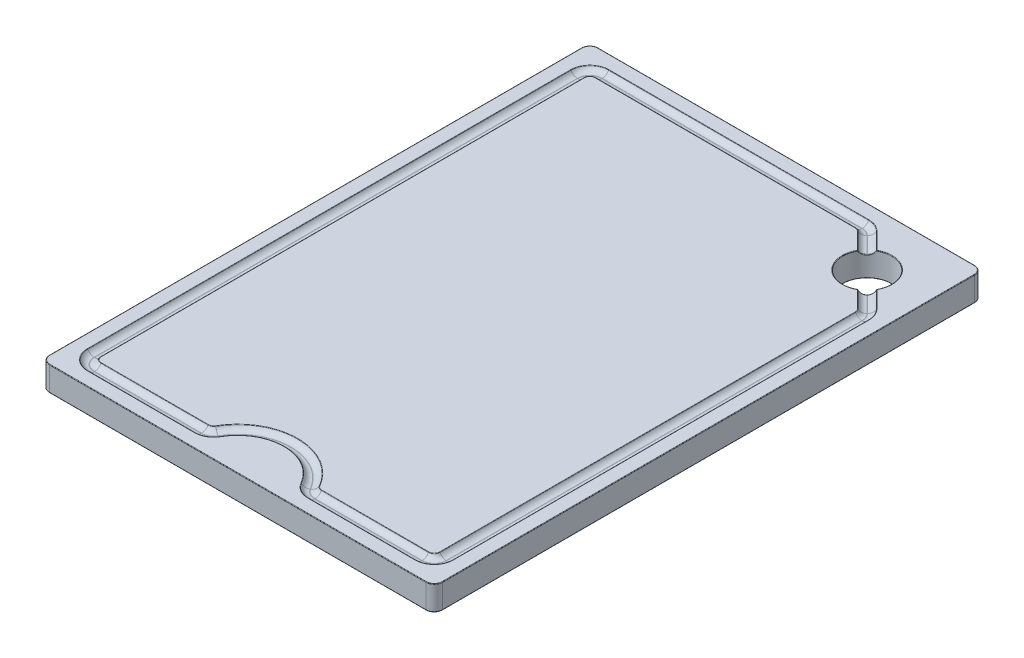
SolidWorks part; units mm, degrees
material "Oak"
ref_plane "Front Plane" through (0, 0, 0) normal (0, 0, 1) x (1, 0, 0)
ref_plane "Top Plane" through (0, 0, 0) normal (0, 1, 0) x (1, 0, 0)
ref_plane "Right Plane" through (0, 0, 0) normal (1, 0, 0) x (0, 0, -1)
sketch "KrausKorePlanSketch" plane through (0, 0, 0) normal (0, 1, 0) x (1, 0, 0)
  line L0 (419.1, 558.8) -> (419.1, 0) construction
  line L1 (0, 0) -> (838.2, 0)
  line L2 (0, 0) -> (0, 558.8)
  line L3 (0, 558.8) -> (838.2, 558.8)
  line L4 (838.2, 0) -> (838.2, 558.8)
  line L5 (0, 279.4) -> (838.2, 279.4) construction
  line L6 (25.4, 241.3) -> (812.8, 241.3) construction
  line L7 (25.4, 457.2) -> (812.8, 457.2)
  line L8 (25.4, 457.2) -> (25.4, 25.4)
  line L9 (25.4, 25.4) -> (812.8, 25.4)
  line L10 (812.8, 457.2) -> (812.8, 25.4)
  line L11 (419.1, 508) -> (749.3, 508) construction
  line L12 (749.3, 558.8) -> (749.3, 457.2) construction
  line L14 (812.8, 444.5) -> (25.4, 444.5)
  line L17 (812.8, 38.1) -> (25.4, 38.1)
  circle A0 centre (685.8, 317.5) radius 44.45
  circle A1 centre (419.1, 508) radius 17.4625
  circle A2 centre (749.3, 508) radius 17.4625
  point P13 (419.1, 457.2)
  dimension "D6" = 88.9
  dimension "D8" = 34.925
  dimension "D1" = 838.2
  dimension "D2" = 558.8
  dimension "D3" = 431.8
  dimension "D4" = 787.4
  dimension "D5" = 101.6
  dimension "D7" = 127
  dimension "D9" = 12.7
  dimension "D10" = 406.4
  dimension "D11" = 127
  dimension "D12" = 50.8
  dimension "D13" = 88.9
sketch "CuttingBoardSketch" plane through (0, 0, 0) normal (0, 1, 0) x (1, 0, 0)
  line L0 (25.4, 241.3) -> (812.8, 241.3) construction
  line L1 (28.575, 454.025) -> (333.375, 454.025)
  line L2 (28.575, 454.025) -> (28.575, 28.575)
  line L3 (28.575, 28.575) -> (333.375, 28.575)
  line L4 (333.375, 454.025) -> (333.375, 28.575)
  line L6 (25.4, 457.2) -> (25.4, 25.4) construction
  line L7 (317.5, 53.975) -> (317.5, 376.2609)
  line L8 (314.7102, 382.9961) -> (262.3461, 435.3602)
  line L9 (255.6109, 438.15) -> (53.975, 438.15)
  line L10 (44.45, 428.625) -> (44.45, 53.975)
  line L11 (53.975, 44.45) -> (136.9809, 44.45)
  line L12 (180.975, 69.85) -> (180.975, 28.575) construction
  line L13 (224.9691, 44.45) -> (307.975, 44.45)
  line L14 (255.6109, 443.3094) -> (53.975, 443.3094)
  line L15 (39.2906, 428.625) -> (39.2906, 53.975)
  line L16 (53.975, 39.2906) -> (136.9809, 39.2906)
  line L17 (224.9691, 39.2906) -> (307.975, 39.2906)
  line L18 (322.6594, 53.975) -> (322.6594, 376.2609)
  line L19 (318.3584, 386.6443) -> (265.9943, 439.0084)
  line L20 (255.6109, 432.9906) -> (53.975, 432.9906)
  line L21 (49.6094, 428.625) -> (49.6094, 53.975)
  line L22 (53.975, 49.6094) -> (136.9809, 49.6094)
  line L23 (224.9691, 49.6094) -> (307.975, 49.6094)
  line L24 (312.3406, 53.975) -> (312.3406, 376.2609)
  line L25 (311.062, 379.3478) -> (258.6978, 431.712)
  arc A0 (145.2298, 49.2125) -> (216.7202, 49.2125) centre (180.975, 28.575) cw
  circle A1 centre (288.5281, 409.1781) radius 19.05
  arc A2 (44.45, 53.975) -> (53.975, 44.45) centre (53.975, 53.975) ccw
  arc A3 (136.9809, 44.45) -> (145.2298, 49.2125) centre (136.9809, 53.975) ccw
  arc A4 (216.7202, 49.2125) -> (224.9691, 44.45) centre (224.9691, 53.975) ccw
  arc A5 (317.5, 53.975) -> (307.975, 44.45) centre (307.975, 53.975) cw
  arc A6 (317.5, 376.2609) -> (314.7102, 382.9961) centre (307.975, 376.2609) ccw
  arc A7 (255.6109, 438.15) -> (262.3461, 435.3602) centre (255.6109, 428.625) cw
  arc A8 (44.45, 428.625) -> (53.975, 438.15) centre (53.975, 428.625) cw
  arc A9 (39.2906, 428.625) -> (53.975, 443.3094) centre (53.975, 428.625) cw
  arc A10 (39.2906, 53.975) -> (53.975, 39.2906) centre (53.975, 53.975) ccw
  arc A11 (136.9809, 39.2906) -> (149.698, 46.6328) centre (136.9809, 53.975) ccw
  arc A12 (149.698, 46.6328) -> (212.252, 46.6328) centre (180.975, 28.575) cw
  arc A13 (212.252, 46.6328) -> (224.9691, 39.2906) centre (224.9691, 53.975) ccw
  arc A14 (322.6594, 53.975) -> (307.975, 39.2906) centre (307.975, 53.975) cw
  arc A15 (322.6594, 376.2609) -> (318.3584, 386.6443) centre (307.975, 376.2609) ccw
  arc A16 (255.6109, 443.3094) -> (265.9943, 439.0084) centre (255.6109, 428.625) cw
  arc A17 (49.6094, 428.625) -> (53.975, 432.9906) centre (53.975, 428.625) cw
  arc A18 (49.6094, 53.975) -> (53.975, 49.6094) centre (53.975, 53.975) ccw
  arc A19 (136.9809, 49.6094) -> (140.7617, 51.7922) centre (136.9809, 53.975) ccw
  arc A20 (140.7617, 51.7922) -> (221.1883, 51.7922) centre (180.975, 28.575) cw
  arc A21 (221.1883, 51.7922) -> (224.9691, 49.6094) centre (224.9691, 53.975) ccw
  arc A22 (312.3406, 53.975) -> (307.975, 49.6094) centre (307.975, 53.975) cw
  arc A23 (312.3406, 376.2609) -> (311.062, 379.3478) centre (307.975, 376.2609) ccw
  arc A24 (255.6109, 432.9906) -> (258.6978, 431.712) centre (255.6109, 428.625) cw
  point P4 (333.375, 241.3)
  point P22 (142.875, 44.45)
  point P27 (219.075, 44.45)
  point P36 (180.975, 69.85)
  dimension "D10" = 38.1
  dimension "D12" = 9.525
  dimension "D1" = 304.8
  dimension "D2" = 425.45
  dimension "D3" = 3.175
  dimension "D4" = 15.875
  dimension "D5" = 15.875
  dimension "D6" = 15.875
  dimension "D7" = 15.875
  dimension "D8" = 41.275
  dimension "D9" = 135
  dimension "D11" = 44.8469
  dimension "D13" = 5.1594
  dimension "D14" = 5.1594
extrude "BoardBoss-Extrude" add sketch "CuttingBoardSketch" against normal blind 15.875 and the other way blind 3.175 contours L4 L3 L2 L1
extrude "BoardDrainCut-Extrude" cut sketch "CuttingBoardSketch<3>" against normal blind 3.175 from offset 3.175 contours L20 A24 L25 A1 L8 A7 L9 A8 L10 A2 L11 A3 A0 A4 L13 A5 L7 A6 A23 L24 A22 L23 A21 A20 A19 L22 A18 L21 A17 | A0 L12 A12 A13 L17 A14 L18 A15 L19 A1 L8 A6 L7 A5 L13 A4 | L12 A0 A3 L11 A2 L10 A8 L9 A7 L8 A1 L19 A16 L14 A9 L15 A10 L16 A11 A12 | L25 A1 L8 | L8 A1 L19 region at (160.5678, 0, -63.9214) region at (184.8491, 0, -67.2703) region at (157.9419, 0, -68.4695) region at (290.3408, 0, -410.9908) region at (286.7155, 0, -407.3655)
sketch "CuttingBoardSketch<3>" plane through (0, 0, 0) normal (0, 1, 0) x (1, 0, 0) same geometry as "CuttingBoardSketch"
fillet "BoardDrainFillet" radius 5.5562 28 edges at (257.2815, 0, -432.6583) (154.7929, 0, -432.9906) (50.888, 0, -431.712) (49.6094, 0, -241.3) (50.888, 0, -50.888) (95.478, 0, -49.6094) (139.1637, 0, -50.1943) (180.975, 0, -75.0094) (222.7863, 0, -50.1943) (266.472, 0, -49.6094) (311.062, 0, -50.888) (312.3406, 0, -215.1179) (312.0083, 0, -377.9315) (284.8799, 0, -405.5299) (95.478, 0, -39.2906) (43.5916, 0, -43.5916) (39.2906, 0, -241.3) (43.5916, 0, -439.0084) (154.7929, 0, -443.3094) (261.2303, 0, -442.1916) (292.1764, 0, -412.8264) (321.5416, 0, -381.8803) (322.6594, 0, -215.1179) (318.3584, 0, -43.5916) (266.472, 0, -39.2906) (217.6269, 0, -41.258) (180.975, 0, -64.6906) (144.3231, 0, -41.258)
extrude "BoardHoleCut-Extrude" cut sketch "CuttingBoardSketch<4>" against normal through all and the other way through all contours A1
sketch "CuttingBoardSketch<4>" plane through (0, 0, 0) normal (0, 1, 0) x (1, 0, 0) same geometry as "CuttingBoardSketch"
fillet "BoardCornersFillet" radius 6.35 4 edges at (333.375, -6.35, -28.575) (28.575, -6.35, -28.575) (28.575, -6.35, -454.025) (333.375, -6.35, -454.025)
fillet "FinishingFillet" radius 0.3969 55 edges at (273.3779, 0.5486, -420.7269) (275.0577, 0, -422.6485) (277.7875, 1.1549, -424.9116) (303.6783, 0.5486, -397.6294) (301.9985, 0, -395.7077) (299.2688, 1.1549, -393.4447) (331.5151, -15.875, -452.1651) (180.975, -15.875, -454.025) (30.4349, -15.875, -452.1651) (28.575, -15.875, -241.3) (30.4349, -15.875, -30.4349) (180.975, -15.875, -28.575) (331.5151, -15.875, -30.4349) (333.375, -15.875, -241.3) (288.5281, -15.875, -390.1281) (312.0083, 3.175, -377.9315) (312.3406, 3.175, -215.1179) (311.062, 3.175, -50.888) (266.472, 3.175, -49.6094) (222.7863, 3.175, -50.1943) (180.975, 3.175, -75.0094) (139.1637, 3.175, -50.1943) (95.478, 3.175, -49.6094) (50.888, 3.175, -50.888) (49.6094, 3.175, -241.3) (50.888, 3.175, -431.712) (154.7929, 3.175, -432.9906) (257.2815, 3.175, -432.6583) (265.3054, 3.175, -425.1044) (275.0577, 3.175, -395.7077) (304.4544, 3.175, -385.9554) (30.4349, 3.175, -30.4349) (28.575, 3.175, -241.3) (30.4349, 3.175, -452.1651) (180.975, 3.175, -454.025) (331.5151, 3.175, -452.1651) (333.375, 3.175, -241.3) (331.5151, 3.175, -30.4349) (180.975, 3.175, -28.575) (261.2303, 3.175, -442.1916) (154.7929, 3.175, -443.3094) (43.5916, 3.175, -439.0084) (39.2906, 3.175, -241.3) (43.5916, 3.175, -43.5916) (95.478, 3.175, -39.2906) (144.3231, 3.175, -41.258) (180.975, 3.175, -64.6906) (217.6269, 3.175, -41.258) (266.472, 3.175, -39.2906) (318.3584, 3.175, -43.5916) (322.6594, 3.175, -215.1179) (321.5416, 3.175, -381.8803) (311.7509, 3.175, -393.2518) (301.9985, 3.175, -422.6485) (272.6018, 3.175, -432.4009)
